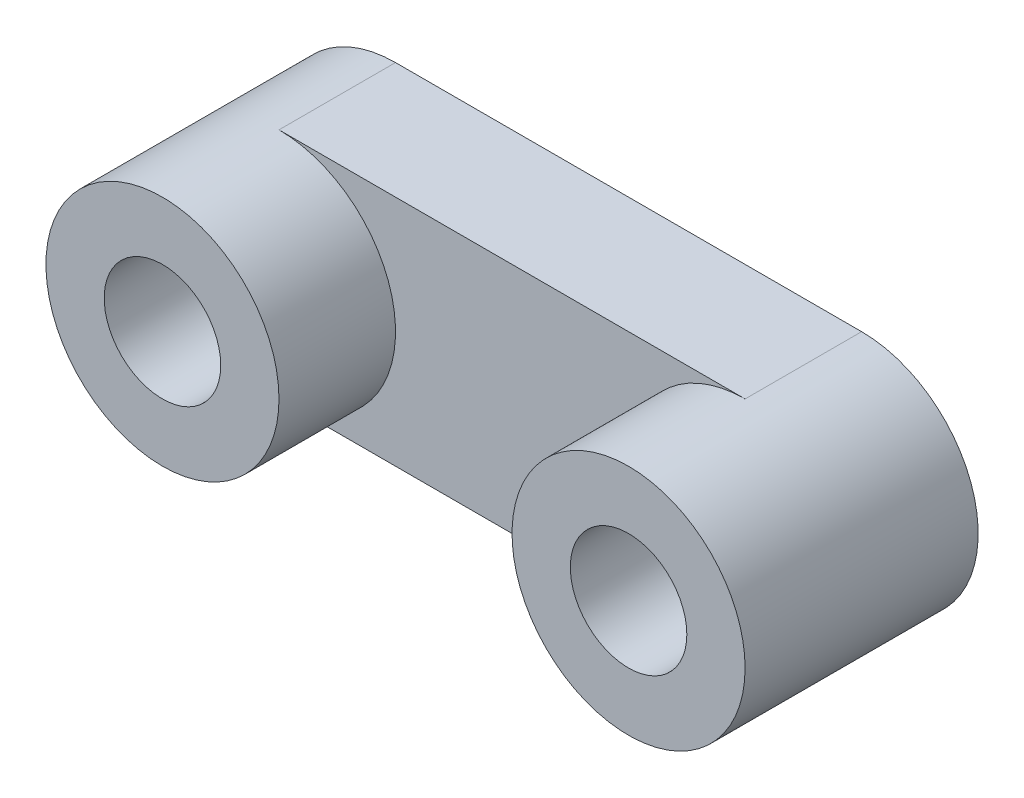
SolidWorks part; units mm, degrees
ref_plane "Piano frontale" through (0, 0, 0) normal (0, 0, 1) x (1, 0, 0)
ref_plane "Piano superiore" through (0, 0, 0) normal (0, 1, 0) x (1, 0, 0)
ref_plane "Piano destro" through (0, 0, 0) normal (1, 0, 0) x (0, 0, -1)
sketch "Schizzo1" plane through (0, 0, 0) normal (0, 0, 1) x (1, 0, 0)
  line L0 (-7.8622, 0) -> (12.1378, 0) construction
  line L1 (-7.8622, 5) -> (12.1378, 5)
  line L2 (-7.8622, -5) -> (12.1378, -5)
  arc A0 (-7.8622, 5) -> (-7.8622, -5) centre (-7.8622, 0) ccw
  arc A1 (12.1378, -5) -> (12.1378, 5) centre (12.1378, 0) ccw
  point P3 (2.1378, 0)
  dimension "D1" = 10
  dimension "D2" = 20
extrude "Estrusione-Estrusione1" add sketch "Schizzo1" along normal blind 5
sketch "Schizzo2" plane through (0, 0, 5) normal (0, 0, 1) x (1, 0, 0)
  line L0 (0, 0) -> (0, 8.3472) construction
  circle A0 centre (-7.8622, 0) radius 5
  arc A2 (-7.8622, 5) -> (-7.8622, -5) centre (-7.8622, 0) ccw construction
  circle A3 centre (-7.8622, 0) radius 2.5
  circle A4 centre (12.1378, 0) radius 5
  circle A5 centre (12.1378, 0) radius 2.5
  point P13 (12.0949, 0)
  dimension "D1" = 10
  dimension "D3" = 10
  dimension "D2" = 0
  dimension "D4" = 20
extrude "Estrusione-Estrusione2" add sketch "Schizzo2" along normal blind 5
